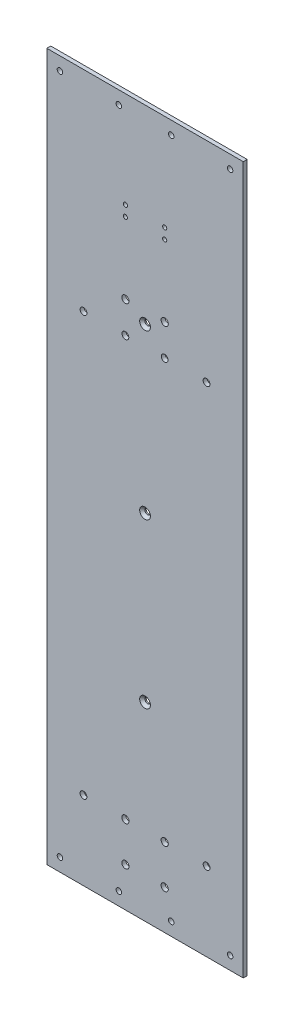
SolidWorks part; units mm, degrees
material "Thornel Mat VMA"
ref_plane "Front" through (0, 0, 0) normal (0, 0, 1) x (1, 0, 0)
ref_plane "Top" through (0, 0, 0) normal (0, 1, 0) x (1, 0, 0)
ref_plane "Right" through (0, 0, 0) normal (1, 0, 0) x (0, 0, -1)
sketch "草图1" plane through (0, 0, 0) normal (0, 0, 1) x (1, 0, 0)
  line L1 (-75, -270) -> (75, -270)
  line L2 (-75, -270) -> (-75, 270)
  line L3 (-75, 270) -> (75, 270)
  line L4 (75, -270) -> (75, 270)
  line L5 (-75, -270) -> (75, 270) construction
  line L6 (-75, 270) -> (75, -270) construction
  point P0 (0, 0)
  dimension "D1" = 150
  dimension "D2" = 540
extrude "凸台-拉伸1" add sketch "草图1" along normal blind 3
sketch "草图2" plane through (0, 0, 0) normal (0, 0, -1) x (-1, 0, 0)
  line L0 (-75, 0) -> (75, 0) construction
  line L1 (-75, -270) -> (-75, 270) construction
  line L2 (75, 270) -> (75, -270) construction
  line L3 (75, -270) -> (-75, -270) construction
  line L4 (0, -270) -> (0, -312.3628) construction
  line L5 (0, 270) -> (0, 297.7999) construction
  line L6 (-75, 270) -> (75, 270) construction
  circle A2 centre (65, -260) radius 2.1
  circle A3 centre (-65, -260) radius 2.1
  circle A6 centre (65, 260) radius 2.1
  circle A7 centre (-65, 260) radius 2.1
  circle A8 centre (-20, -260) radius 2.1
  circle A9 centre (20, -260) radius 2.1
  circle A10 centre (20, 260) radius 2.1
  circle A11 centre (-20, 260) radius 2.1
  circle A16 centre (15, 196.5) radius 1.6
  circle A17 centre (15, 188.5) radius 1.6
  circle A18 centre (-15, 196.5) radius 1.6
  circle A19 centre (-15, 188.5) radius 1.6
  dimension "D1" = 45
  dimension "D2" = 45
  dimension "D3" = 3.2
  dimension "D4" = 4.2
  dimension "D5" = 10
  dimension "D6" = 10
  dimension "D7" = 4.2
  dimension "D8" = 10
  dimension "D9" = 10
  dimension "D10" = 30
  dimension "D11" = 8
  dimension "D12" = 73.5
extrude "切除-拉伸1" cut sketch "草图2" against normal through all
sketch "草图3" plane through (0, 0, 3) normal (0, 0, 1) x (1, 0, 0)
  line L1 (75, -270) -> (75, 270) construction
  circle A0 centre (65, 30) radius 1.5
  circle A1 centre (65, -30) radius 1.5
  dimension "D1" = 3
  dimension "D2" = 10
  dimension "D3" = 30
  dimension "D4" = 3
  dimension "D5" = 30
  dimension "D6" = 10
sketch "草图4" plane through (0, 0, 3) normal (0, 0, 1) x (1, 0, 0)
  line L0 (0, 0) -> (98.7159, 0) construction
  circle A0 centre (0, 125) radius 2.1
  circle A1 centre (0, -125) radius 2.1
  circle A2 centre (0, 0) radius 2.1
  dimension "D1" = 250
  dimension "D2" = 4.2
extrude "切除-拉伸2" cut sketch "草图4" against normal up to next
chamfer "倒角1" distance 2 angle 45 3 edges at (2.1, 0, 3) (-2.1, -125, 3) (2.1, 125, 3)
sketch "草图6" plane through (0, 0, 3) normal (0, 0, 1) x (1, 0, 0)
  line L0 (0, -286.6484) -> (0, 69.1326) construction
  line L1 (-75, -270) -> (75, -270) construction
  line L2 (-75, 270) -> (-75, -270) construction
  line L3 (75, -270) -> (75, 270) construction
  line L6 (75, 270) -> (-75, 270) construction
  circle A1 centre (15, -210) radius 2.6
  circle A4 centre (-15, -210) radius 2.6
  circle A5 centre (47, -210) radius 2.6
  circle A6 centre (-47, -210) radius 2.6
  circle A9 centre (-47, 110) radius 2.6
  circle A10 centre (-15, 110.0004) radius 2.6
  circle A11 centre (15, 110.0009) radius 2.6
  circle A12 centre (47, 110.0013) radius 2.6
  dimension "D1" = 5.2
  dimension "D2" = 15
  dimension "D3" = 60
  dimension "D4" = 32
  dimension "D5" = 5.2
  dimension "D6" = 5.2
  dimension "D7" = 5.2
  dimension "D8" = 5.2
  dimension "D9" = 32
  dimension "D10" = 30
  dimension "D11" = 32
  dimension "D12" = 28
  dimension "D13" = 28
  dimension "D14" = 160
extrude "切除-拉伸4" cut sketch "草图6" against normal up to next
sketch "草图7" plane through (0, 0, 3) normal (0, 0, 1) x (1, 0, 0)
  line L4 (75, -270) -> (75, 270)
  line L5 (75, 270) -> (-75, 270)
  line L6 (-75, 270) -> (-75, -270)
  line L7 (-75, -270) -> (75, -270)
  line L8 (75, -270) -> (75, 270)
  line L9 (75, 270) -> (-75, 270)
  line L10 (-75, 270) -> (-75, -270)
  line L11 (-75, -270) -> (75, -270)
  circle A2 centre (-15, 134) radius 2.75
  circle A3 centre (15, 134) radius 2.75
  dimension "D2" = 136
  dimension "D3" = 5.5
  dimension "D5" = 30
  dimension "D6" = 5.5
  dimension "D7" = 60
  dimension "D4" = 136
  dimension "D1" = 0
extrude "切除-拉伸5" cut sketch "草图7" against normal up to next contours A2 | A3 region at (-15, 134, 3)
sketch "草图8" plane through (0, 0, 3) normal (0, 0, 1) x (1, 0, 0)
  line L4 (75, -270) -> (75, 270)
  line L5 (75, 270) -> (-75, 270)
  line L6 (-75, 270) -> (-75, -270)
  line L7 (-75, -270) -> (75, -270)
  line L8 (75, -270) -> (75, 270)
  line L9 (75, 270) -> (-75, 270)
  line L10 (-75, 270) -> (-75, -270)
  line L11 (-75, -270) -> (75, -270)
  circle A2 centre (-15, -210) radius 2.75
  circle A3 centre (15, -210) radius 2.75
  dimension "D2" = 5.5
  dimension "D3" = 5.5
  dimension "D4" = 30
  dimension "D5" = 60
  dimension "D6" = 60
  dimension "D7" = 60
  dimension "D1" = 0
extrude "切除-拉伸6" cut sketch "草图8" against normal up to next contours A2 | A3 region at (-15, -210, 3) region at (15, -210, 3)
sketch "草图9" plane through (0, 0, 3) normal (0, 0, 1) x (1, 0, 0)
  line L0 (0, -270) -> (0, -79.9483) construction
  line L1 (-75, -270) -> (75, -270) construction
  circle A0 centre (-15, -240) radius 2.75
  circle A1 centre (15, -240) radius 2.75
  dimension "D1" = 5.5
  dimension "D2" = 30
  dimension "D3" = 30
extrude "切除-拉伸7" cut sketch "草图9" against normal blind 10
